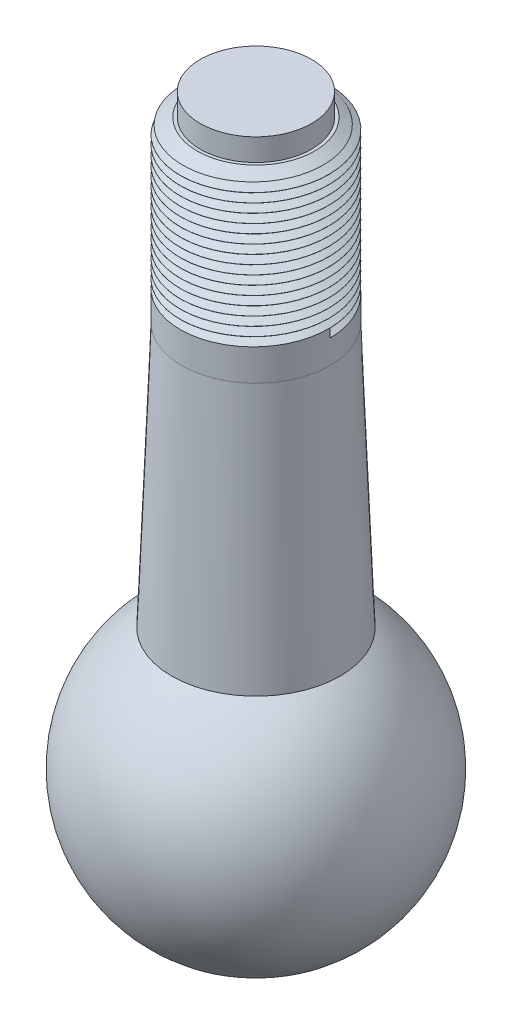
SolidWorks part; units mm, degrees
ref_plane "Front Plane" through (0, 0, 0) normal (0, 0, 1) x (1, 0, 0)
ref_plane "Top Plane" through (0, 0, 0) normal (0, 1, 0) x (1, 0, 0)
ref_plane "Right Plane" through (0, 0, 0) normal (1, 0, 0) x (0, 0, -1)
sketch "Sketch1" plane through (0, 0, 0) normal (1, 0, 0) x (0, 0, -1)
  line L0 (0, 0) -> (0, 25.4) construction
  line L1 (0, 0) -> (0, -25.4) construction
  line L2 (0, 25.4) -> (0, -25.4)
  arc A0 (0, -25.4) -> (0, 25.4) centre (0, 0) cw
  dimension "D1" = 25.4
revolve "Revolve1" add sketch "Sketch1" angle 360 about L2
sketch "Sketch2" plane through (0, 0, 0) normal (0, 1, 0) x (1, 0, 0)
  circle A0 centre (0, 0) radius 15.24
  dimension "D1" = 30.48
extrude "Boss-Extrude1" add sketch "Sketch2" along normal blind 66.04 draft 2.2
sketch "Sketch3" plane through (0, 66.04, 0) normal (0, 1, 0) x (1, 0, 0)
  circle A0 centre (0, 0) radius 12.703
  circle A1 centre (0, 0) radius 12.703 construction
extrude "Boss-Extrude2" add sketch "Sketch3" along normal blind 34.29
ref_plane "Plane1" through (0, 101.346, 0) normal (0, 1, 0) x (-1, 0, 0)
sketch "Sketch5" plane through (0, 101.346, 0) normal (0, 1, 0) x (-1, 0, 0)
  circle A0 centre (0, 0) radius 12.703
  circle A1 centre (0, 0) radius 12.703 construction
curve "Helix/Spiral1" pitch 1.524 height 30.48 radius 12.703 centre (0, 101.346, 0) axis (0, -1, 0) start towards (1, 0, 0)
sketch "Sketch7" plane through (0, 100.33, 0) normal (0, 1, 0) x (1, 0, 0)
  circle A0 centre (0, 0) radius 9.525
  circle A1 centre (0, 0) radius 16.6011
  dimension "D1" = 19.05
  dimension "D2" = 33.2022
extrude "Cut-Extrude1" cut sketch "Sketch7" against normal blind 3.81
chamfer "Chamfer1" distance 1.524 angle 60 1 edges at (0, 96.52, 12.703) first distance on face at (0, 66.04, 12.703)
sketch "Sketch6" plane through (0, 0, 0) normal (0, 0, 1) x (1, 0, 0)
  line L0 (12.703, 102.0953) -> (12.703, 100.5967) construction
  line L1 (12.703, 101.346) -> (11.4052, 101.346) construction
  line L3 (12.703, 102.0953) -> (11.4052, 101.346)
  line L4 (11.4052, 101.346) -> (12.703, 100.5967)
  arc A0 (12.703, 100.5967) -> (12.703, 102.0953) centre (12.703, 101.346) ccw
  dimension "D2" = 0.7493
  dimension "D1" = 60
sweep "Cut-Sweep1" cut profiles "Sketch6" path "Helix/Spiral1" align with end faces yes
